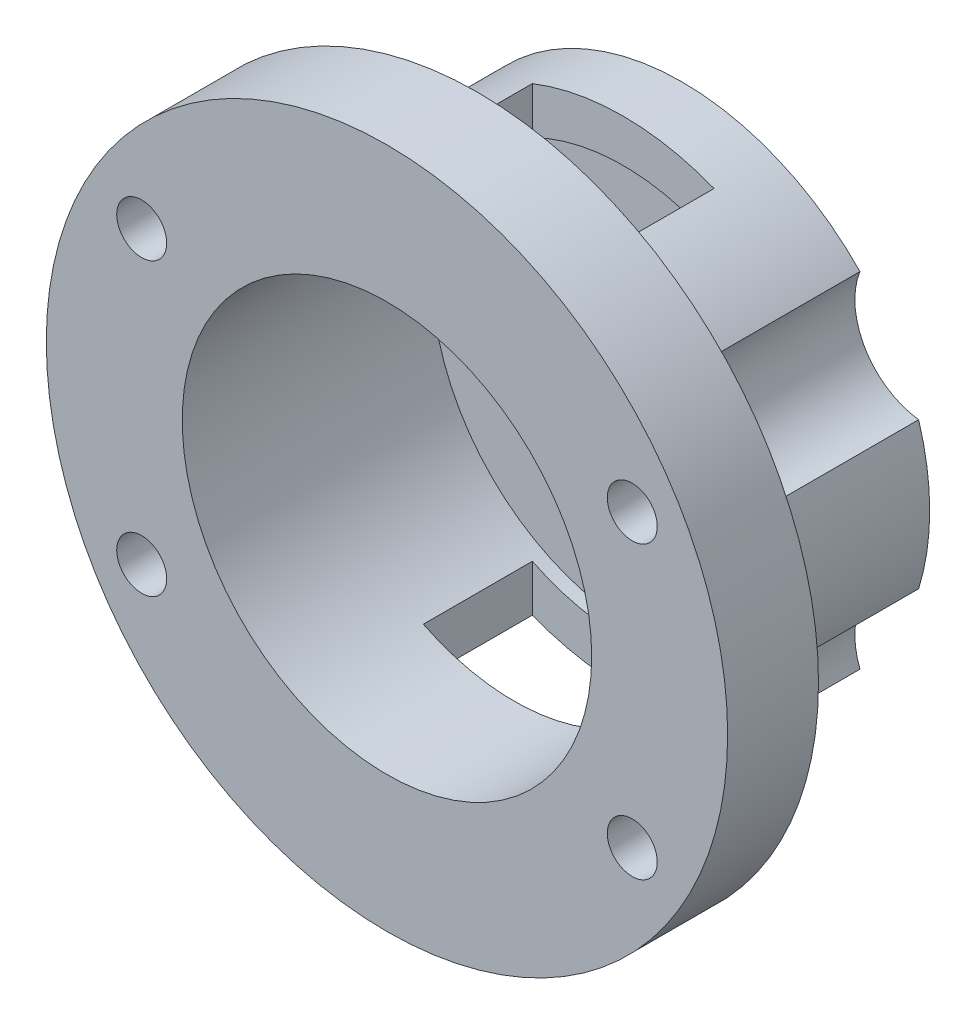
SolidWorks part; units mm, degrees
ref_plane "前视基准面" through (0, 0, 0) normal (0, 0, 1) x (1, 0, 0)
ref_plane "上视基准面" through (0, 0, 0) normal (0, 1, 0) x (1, 0, 0)
ref_plane "右视基准面" through (0, 0, 0) normal (1, 0, 0) x (0, 0, -1)
other "Configuration Table"
sketch "草图1" plane through (0, 0, 0) normal (0, 0, 1) x (1, 0, 0)
  line L0 (-27, 16) -> (27, -16) construction
  line L1 (-27, 16) -> (27, 16) construction
  line L2 (-27, 16) -> (-27, -16) construction
  line L3 (-27, -16) -> (27, -16) construction
  line L4 (27, 16) -> (27, -16) construction
  line L5 (27, 16) -> (-27, -16) construction
  line L6 (0, 0) -> (37.5, 0) construction
  line L12 (12.7, 3.25) -> (12.7, -3.25) construction
  line L13 (5.95, 0) -> (19.45, 0) construction
  circle A0 centre (0, 0) radius 37.5
  circle A1 centre (-27, 16) radius 2.75
  circle A2 centre (27, 16) radius 2.75
  circle A3 centre (-27, -16) radius 2.75
  circle A4 centre (27, -16) radius 2.75
  point P7 (0, 0)
  point P11 (12.7, 0)
  dimension "D1" = 75
  dimension "D4" = 5.5
  dimension "D2" = 32
  dimension "D3" = 54
  dimension "D7" = 12.7
extrude "凸台-拉伸1" add sketch "草图1" along normal blind 20
sketch "草图2" plane through (0, 0, 20) normal (0, 0, 1) x (1, 0, 0)
  circle A0 centre (0, 0) radius 22.5362
extrude "切除-拉伸1" cut sketch "草图2" against normal blind 12
sketch "草图8" plane through (0, 0, 0) normal (0, 0, -1) x (-1, 0, 0)
  circle A0 centre (0, 0) radius 37.5
  circle A1 centre (0, 0) radius 27.2402
extrude "切除-拉伸4" cut sketch "草图8" against normal blind 10
sketch "草图9" plane through (0, 0, 0) normal (0, 0, -1) x (-1, 0, 0)
  circle A1 centre (-27, 16) radius 8
  circle A2 centre (27, 16) radius 8
  circle A3 centre (-27, -16) radius 8
  circle A4 centre (27, -16) radius 8
  dimension "D1" = 16
  dimension "D2" = 16
  dimension "D3" = 16
  dimension "D4" = 16
extrude "切除-拉伸5" cut sketch "草图9" against normal blind 10
sketch "草图10" plane through (0, 0, 0) normal (0, 0, -1) x (-1, 0, 0)
  arc A8 (-19.5652, -18.9535) -> (19.5652, -18.9535) centre (0, 0) ccw
  arc A9 (26.0204, -8.0602) -> (19.5652, -18.9535) centre (27, -16) ccw
  arc A10 (26.0204, -8.0602) -> (26.0204, 8.0602) centre (0, 0) ccw
  arc A11 (19.5652, 18.9535) -> (26.0204, 8.0602) centre (27, 16) ccw
  arc A12 (19.5652, 18.9535) -> (-19.5652, 18.9535) centre (0, 0) ccw
  arc A13 (-26.0204, 8.0602) -> (-19.5652, 18.9535) centre (-27, 16) ccw
  arc A14 (-26.0204, 8.0602) -> (-26.0204, -8.0602) centre (0, 0) ccw
  arc A15 (-19.5652, -18.9535) -> (-26.0204, -8.0602) centre (-27, -16) ccw
  arc A16 (-19.5652, -18.9535) -> (19.5652, -18.9535) centre (0, 0) ccw
  arc A17 (26.0204, -8.0602) -> (19.5652, -18.9535) centre (27, -16) ccw
  arc A18 (26.0204, -8.0602) -> (26.0204, 8.0602) centre (0, 0) ccw
  arc A19 (19.5652, 18.9535) -> (26.0204, 8.0602) centre (27, 16) ccw
  arc A20 (19.5652, 18.9535) -> (-19.5652, 18.9535) centre (0, 0) ccw
  arc A21 (-26.0204, 8.0602) -> (-19.5652, 18.9535) centre (-27, 16) ccw
  arc A22 (-26.0204, 8.0602) -> (-26.0204, -8.0602) centre (0, 0) ccw
  arc A23 (-19.5652, -18.9535) -> (-26.0204, -8.0602) centre (-27, -16) ccw
  dimension "D1" = 0
extrude "凸台-拉伸2" add sketch "草图10" along normal blind 10
sketch "草图11" plane through (0, 0, -10) normal (0, 0, -1) x (-1, 0, 0)
  circle A0 centre (0, 0) radius 45
  dimension "D1" = 90
extrude "凸台-拉伸3" add sketch "草图11" along normal blind 5
sketch "草图13" plane through (0, 0, -15) normal (0, 0, -1) x (-1, 0, 0)
  circle A0 centre (0, 0) radius 36.416 construction
  circle A1 centre (0, 36.416) radius 1.5
  circle A2 centre (-36.416, 0) radius 1.5
  circle A3 centre (0, -36.416) radius 1.5
  circle A4 centre (36.416, 0) radius 1.5
  dimension "D1" = 3
  dimension "D2" = 3
  dimension "D3" = 3
  dimension "D4" = 3
  dimension "D5" = 51.5
extrude "切除-拉伸6" cut sketch "草图13" against normal blind 10
sketch "草图14" plane through (0, 0, 8) normal (0, 0, 1) x (1, 0, 0)
  circle A0 centre (0, 0) radius 22.5362
extrude "切除-拉伸7" cut sketch "草图14" against normal through all
sketch "草图15" plane through (0, 0, 0) normal (0, 1, 0) x (1, 0, 0)
  line L0 (-19.5652, 10) -> (19.5652, 10) construction
  line L1 (-10, 6) -> (10, 6)
  line L2 (-10, 6) -> (-10, -6)
  line L3 (-10, -6) -> (10, -6)
  line L4 (10, 6) -> (10, -6)
  line L5 (19.5652, -10) -> (-19.5652, -10) construction
  dimension "D1" = 4
  dimension "D2" = 4
  dimension "D3" = 10
  dimension "D4" = 10
extrude "切除-拉伸8" cut sketch "草图15" against normal through all and the other way through all
ref_plane "基准面1" through (0, 0, -10) normal (0, 0, 1) x (1, 0, 0)
sketch "草图17" plane through (0, 0, -10) normal (0, 0, 1) x (1, 0, 0)
  circle A0 centre (0, 0) radius 45
extrude "切除-拉伸11" cut sketch "草图17" against normal blind 10
sketch "草图19" plane through (0, 0, -10) normal (0, 0, -1) x (-1, 0, 0)
  circle A0 centre (0, 0) radius 22.5362
extrude "凸台-拉伸4" add sketch "草图19" along normal blind 2.5 and the other way blind 2.5
sketch "草图21" plane through (0, 0, -12.5) normal (0, 0, -1) x (-1, 0, 0)
  circle A0 centre (0, 0) radius 7 construction
  circle A1 centre (0, 7) radius 1.5
  circle A2 centre (-7, 0) radius 1.5
  circle A3 centre (7, 0) radius 1.5
  circle A4 centre (0, -7) radius 1.5
  dimension "D1" = 14
  dimension "D2" = 3
  dimension "D3" = 3
  dimension "D4" = 3
  dimension "D5" = 3
extrude "切除-拉伸12" cut sketch "草图21" against normal through all
sketch "草图22" plane through (0, 0, -10) normal (0, 0, -1) x (-1, 0, 0)
  circle A0 centre (0, 0) radius 22.5362
  arc A8 (-26.0204, 8.0602) -> (-26.0204, -8.0602) centre (0, 0) ccw
  arc A9 (-19.5652, -18.9535) -> (-26.0204, -8.0602) centre (-27, -16) ccw
  arc A10 (-19.5652, -18.9535) -> (19.5652, -18.9535) centre (0, 0) ccw
  arc A11 (26.0204, -8.0602) -> (19.5652, -18.9535) centre (27, -16) ccw
  arc A12 (26.0204, -8.0602) -> (26.0204, 8.0602) centre (0, 0) ccw
  arc A13 (19.5652, 18.9535) -> (26.0204, 8.0602) centre (27, 16) ccw
  arc A14 (19.5652, 18.9535) -> (-19.5652, 18.9535) centre (0, 0) ccw
  arc A15 (-26.0204, 8.0602) -> (-19.5652, 18.9535) centre (-27, 16) ccw
  arc A16 (-26.0204, 8.0602) -> (-26.0204, -8.0602) centre (0, 0) ccw
  arc A17 (-19.5652, -18.9535) -> (-26.0204, -8.0602) centre (-27, -16) ccw
  arc A18 (-19.5652, -18.9535) -> (19.5652, -18.9535) centre (0, 0) ccw
  arc A19 (26.0204, -8.0602) -> (19.5652, -18.9535) centre (27, -16) ccw
  arc A20 (26.0204, -8.0602) -> (26.0204, 8.0602) centre (0, 0) ccw
  arc A21 (19.5652, 18.9535) -> (26.0204, 8.0602) centre (27, 16) ccw
  arc A22 (19.5652, 18.9535) -> (-19.5652, 18.9535) centre (0, 0) ccw
  arc A23 (-26.0204, 8.0602) -> (-19.5652, 18.9535) centre (-27, 16) ccw
  dimension "D1" = 0
extrude "凸台-拉伸6" add sketch "草图22" along normal blind 2.5
